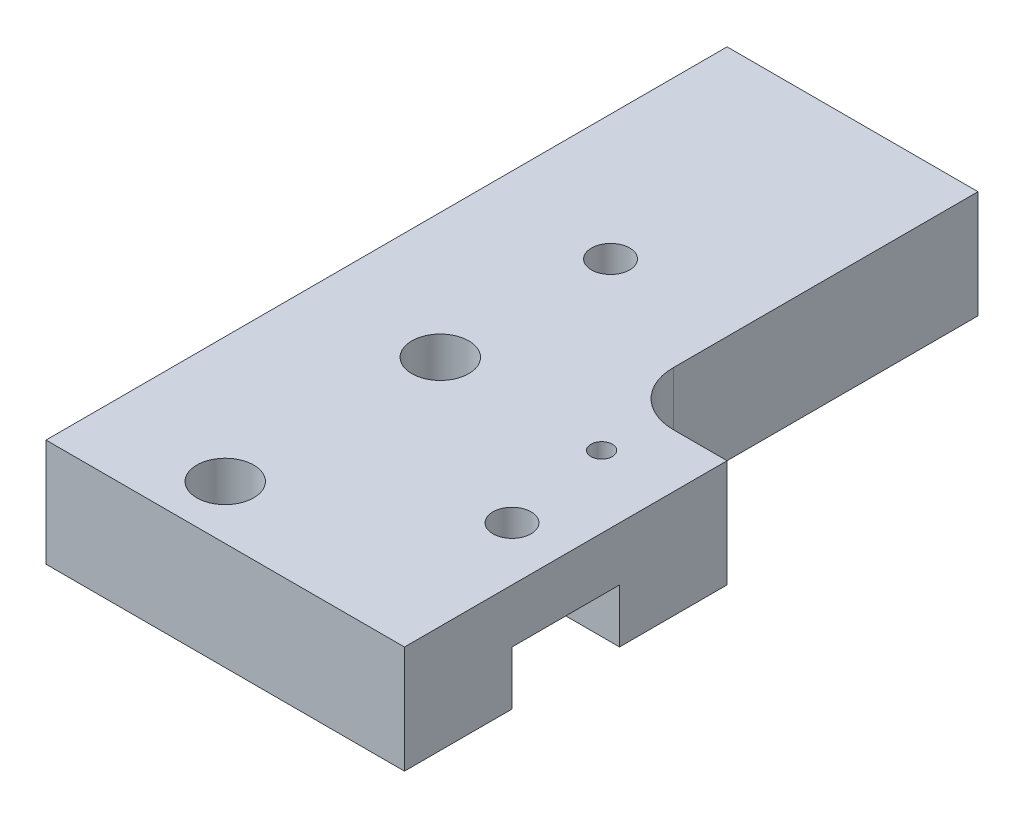
SolidWorks part; units mm, degrees
material "6061-T6 (SS)"
ref_plane "Front" through (0, 0, 0) normal (0, 0, 1) x (1, 0, 0)
ref_plane "Top" through (0, 0, 0) normal (0, 1, 0) x (1, 0, 0)
ref_plane "Right" through (0, 0, 0) normal (1, 0, 0) x (0, 0, -1)
sketch "Sketch1" plane through (0, 0, 0) normal (0, 1, 0) x (1, 0, 0)
  line L1 (-31.75, -28.575) -> (31.75, -28.575)
  line L2 (-31.75, -28.575) -> (-31.75, 28.575)
  line L3 (-31.75, 28.575) -> (31.75, 28.575)
  line L4 (31.75, -28.575) -> (31.75, 28.575)
  line L5 (-31.75, -28.575) -> (31.75, 28.575) construction
  line L6 (-31.75, 28.575) -> (31.75, -28.575) construction
  point P0 (0, 0)
  dimension "D1" = 63.5
  dimension "D2" = 57.15
extrude "Boss-Extrude1" add sketch "Sketch1" along normal blind 19.05
sketch "Sketch2" plane through (0, 0, 0) normal (0, -1, 0) x (1, 0, 0)
  line L0 (31.75, 28.575) -> (31.75, -28.575) construction
  line L1 (-31.75, -9.525) -> (31.75, -9.525)
  line L2 (-31.75, -9.525) -> (-31.75, 9.525)
  line L3 (-31.75, 9.525) -> (31.75, 9.525)
  line L4 (31.75, -9.525) -> (31.75, 9.525)
  line L5 (-31.75, -9.525) -> (31.75, 9.525) construction
  line L6 (-31.75, 9.525) -> (31.75, -9.525) construction
  point P0 (0, 0)
  dimension "D1" = 19.05
extrude "Cut-Extrude1" cut sketch "Sketch2" against normal blind 9.525
sketch "Sketch3" plane through (0, 0, 0) normal (0, -1, 0) x (1, 0, 0)
  line L0 (-31.75, 28.575) -> (31.75, 28.575) construction
  line L1 (3.175, 28.575) -> (15.875, 28.575)
  line L2 (3.175, 28.575) -> (3.175, -28.575)
  line L3 (3.175, -28.575) -> (15.875, -28.575)
  line L4 (15.875, 28.575) -> (15.875, -28.575)
  line L5 (31.75, -28.575) -> (-31.75, -28.575) construction
  line L6 (31.75, 28.575) -> (31.75, 9.525) construction
  dimension "D1" = 12.7
  dimension "D2" = 15.875
extrude "Cut-Extrude2" [suppressed] cut sketch "Sketch3" against normal up to surface (6.35 mm away) up to face at (0, 9.525, 0)
sketch "Sketch4" plane through (0, 9.525, 0) normal (0, -1, 0) x (1, 0, 0)
  line L0 (31.75, 0) -> (22.225, 0) construction
  line L1 (31.75, -9.525) -> (31.75, 9.525) construction
  line L2 (9.525, 28.575) -> (9.525, 19.05) construction
  dimension "D1" = 9.525
sketch "Sketch7" plane through (0, 0, 0) normal (0, 1, 0) x (1, 0, 0)
  line L0 (-9.525, 28.575) -> (-9.525, 19.05) construction
  line L1 (31.75, 28.575) -> (-31.75, 28.575) construction
  line L2 (-9.525, 19.05) -> (-9.525, 9.525) construction
  line L3 (-9.525, -19.05) -> (-9.525, -28.575) construction
  line L4 (-31.75, -28.575) -> (31.75, -28.575) construction
  line L5 (-31.75, 28.575) -> (-31.75, -28.575) construction
  line L10 (-31.75, 9.525) -> (31.75, 9.525) construction
  dimension "D2" = 22.225
hole_wizard "3/8 Clearance Hole1" positions "Sketch9" profile "Sketch8" hole size "3/8" standard "ANSI Inch" end condition through all
sketch "Sketch9" plane through (0, 19.05, 0) normal (0, 1, 0) x (1, 0, 0)
  point P0 (-9.525, 19.05)
  point P3 (-9.525, -19.05)
sketch "Sketch8" plane through (-9.525, 19.05, -19.05) normal (1, 0, 0) x (0, 0, 1)
  line L0 (0, 0) -> (0, 19.05)
  line L1 (0, 19.05) -> (5.0419, 19.05)
  line L2 (5.0419, 19.05) -> (5.0419, 0)
  line L5 (5.0419, 0) -> (0, 0)
  line L11 (0, -6.35) -> (0, 107.95) construction
  dimension "Thru Hole Dia." = 10.0838
  dimension "Thru Hole Depth" = 19.05
sketch "Sketch10" plane through (0, 0, -28.575) normal (0, 0, -1) x (-1, 0, 0)
  line L1 (31.75, 19.05) -> (-31.75, 19.05)
  line L2 (31.75, 19.05) -> (31.75, 0)
  line L3 (31.75, 0) -> (-31.75, 0)
  line L4 (-31.75, 19.05) -> (-31.75, 0)
extrude "Boss-Extrude2" add sketch "Sketch10" along normal blind 63.5
sketch "Sketch11" plane through (0, 0, 0) normal (0, -1, 0) x (1, 0, 0)
  line L0 (31.75, -92.075) -> (-31.75, -92.075) construction
  line L1 (-19.05, -92.075) -> (0, -92.075)
  line L2 (-19.05, -92.075) -> (-19.05, -31.75)
  line L3 (-19.05, -31.75) -> (0, -31.75)
  line L4 (0, -92.075) -> (0, -31.75)
  line L5 (0, -39.2296) -> (-9.525, -39.2296) construction
  line L7 (-31.75, -9.525) -> (-31.75, 9.525) construction
  line L8 (-9.525, -28.575) -> (-9.525, -39.2296) construction
  line L9 (-9.525, -28.575) -> (-9.525, -19.05) construction
  circle A0 centre (-9.525, -19.05) radius 5.0419 construction
  dimension "D1" = 9.525
  dimension "D2" = 12.7
extrude "Cut-Extrude3" cut sketch "Sketch11" against normal up to surface (9.525 mm away) up to face at (0, 9.525, 0)
fillet "Fillet1" radius 4.7625 2 edges at (0, 4.7625, -31.75) (-19.05, 4.7625, -31.75)
sketch "Sketch12" plane through (0, 9.525, 0) normal (0, -1, 0) x (1, 0, 0)
  line L0 (0, -36.5125) -> (-9.525, -36.5125) construction
  line L1 (-9.525, -36.5125) -> (-9.525, -49.2125) construction
  arc A0 (0, -36.5125) -> (-4.7625, -31.75) centre (-4.7625, -36.5125) ccw construction
  dimension "D1" = 9.525
  dimension "D2" = 12.7
hole_wizard "1/4 Clearance Hole1" positions "Sketch6" profile "Sketch5" hole size "1/4" standard "ANSI Inch" end condition through all
sketch "Sketch6" plane through (0, 9.525, 0) normal (0, -1, 0) x (-1, 0, 0)
  point P3 (-22.225, 0)
  point P9 (9.525, 49.2125)
sketch "Sketch5" plane through (22.225, 9.525, 0) normal (1, 0, 0) x (0, 0, -1)
  line L0 (0, 0) -> (0, 9.525)
  line L1 (0, 9.525) -> (3.3782, 9.525)
  line L2 (3.3782, 9.525) -> (3.3782, 0)
  line L5 (3.3782, 0) -> (0, 0)
  line L11 (0, -6.35) -> (0, 107.95) construction
  dimension "Thru Hole Dia." = 6.7564
  dimension "Thru Hole Depth" = 9.525
sketch "Sketch13" plane through (0, 0, 0) normal (0, -1, 0) x (1, 0, 0)
  line L0 (12.7, -92.075) -> (12.7, -28.575)
  line L1 (31.75, -92.075) -> (0, -92.075) construction
  line L2 (12.7, -28.575) -> (31.75, -28.575)
  line L3 (31.75, -9.525) -> (31.75, -92.075) construction
  line L4 (31.75, -28.575) -> (31.75, -92.075)
  line L5 (31.75, -92.075) -> (12.7, -92.075)
  line L6 (-31.75, 28.575) -> (31.75, 28.575) construction
  dimension "D1" = 19.05
  dimension "D2" = 57.15
extrude "Cut-Extrude5" cut sketch "Sketch13" against normal through all
fillet "Fillet2" radius 9.525 1 edges at (12.7, 9.525, -28.575)
sketch "Sketch14" plane through (0, 19.05, 0) normal (0, 1, 0) x (1, 0, 0)
  line L0 (31.75, 19.05) -> (19.05, 19.05) construction
  line L1 (31.75, -28.575) -> (31.75, 28.575) construction
  line L2 (-31.75, -28.575) -> (31.75, -28.575) construction
  dimension "D1" = 12.7
  dimension "D2" = 47.625
hole_wizard "#10-24 Tapped Hole1" positions "Sketch16" profile "Sketch15" tap size "#10-24" standard "ANSI Inch" end condition through all
sketch "Sketch16" plane through (0, 19.05, 0) normal (0, 1, 0) x (1, 0, 0)
  point P0 (19.05, 19.05)
sketch "Sketch15" plane through (19.05, 19.05, -19.05) normal (1, 0, 0) x (0, 0, 1)
  line L0 (0, 0) -> (0, 19.05)
  line L1 (0, 19.05) -> (1.8986, 19.05)
  line L2 (1.8986, 19.05) -> (1.8986, 0)
  line L5 (1.8986, 0) -> (0, 0)
  line L11 (0, -6.35) -> (0, 107.95) construction
  dimension "Thru Tap Drill Dia." = 3.7973
  dimension "Thru Tap Drill Depth" = 19.05
cosmetic thread "Hole Thread1" parameters "D2"=4.826
